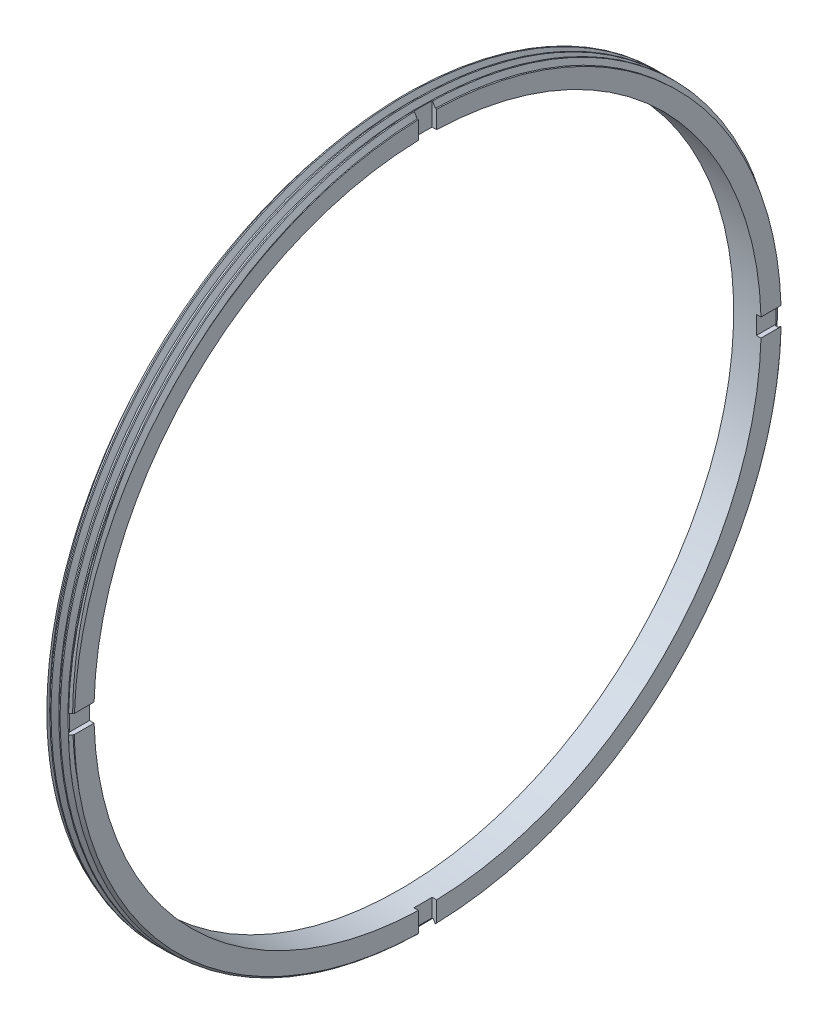
SolidWorks part; units mm, degrees
ref_plane "Přední rovina" through (0, 0, 0) normal (0, 0, 1) x (1, 0, 0)
ref_plane "Horní rovina" through (0, 0, 0) normal (0, 1, 0) x (1, 0, 0)
ref_plane "Pravá rovina" through (0, 0, 0) normal (1, 0, 0) x (0, 0, -1)
sketch "Skica1" plane through (0, 0, 0) normal (0, 0, 1) x (1, 0, 0)
  line L0 (0, 0) -> (50000, 0) construction
  line L1 (0, 36.5) -> (3, 36.5)
  line L2 (0, 36.5) -> (0, 39)
  line L3 (0, 39) -> (3, 39)
  line L4 (3, 36.5) -> (3, 39)
  dimension "D1" = 36.5
  dimension "D2" = 39
  dimension "D3" = 3
revolve "Rotovat1" add sketch "Skica1" angle 360 about L0
chamfer "Zkosení1" distance 0.3 2 edges at (3, 0, 39) (0, 0, 39)
thread "Závit1" pitch 1 start angle 0, offset 1, length 0, pitch 1, diameter 78
ref_plane "Rovina1" through (-0.7, 0, -39) normal (0, -1, 0) x (0, 0, -1)
sketch "Profil závitu1" plane through (-0.7, 0, -39) normal (0, -1, 0) x (0, 0, -1)
  line L0 (0, 0) -> (0, 1) construction
  line L11 (0, 0) -> (0, 0.875)
  line L12 (0, 0.875) -> (-0.5413, 0.5625)
  line L13 (-0.5413, 0.5625) -> (-0.5413, 0.3125)
  line L15 (-0.5413, 0.3125) -> (0, 0)
  line L17 (-0.5413, 0.4375) -> (0, 0.4375) construction
  point P2 (0, 0)
  dimension "Pitch" = 1
  dimension "Profile_Angle" = 60
  dimension "Profile_Land" = 0.25
  dimension "Profile_Height" = 0.5413
sketch "Skica5" plane through (0, 0, 0) normal (0, 1, 0) x (1, 0, 0)
  line L0 (0, 0) -> (3, 0) construction
  line L1 (3, 24.8886) -> (3, 38.6978) construction
  line L2 (2.5, 1) -> (3.5, 1)
  line L3 (2.5, 1) -> (2.5, -1)
  line L4 (2.5, -1) -> (3.5, -1)
  line L5 (3.5, 1) -> (3.5, -1)
  line L6 (2.5, 1) -> (3.5, -1) construction
  line L7 (2.5, -1) -> (3.5, 1) construction
  dimension "D1" = 2
  dimension "D2" = 1
extrude "Odebrat vysunutím1" cut sketch "Skica5" against normal through all both and the other way through all
pattern_circular "Kruhové pole1" count 2 every 90 about axis through (0, 0, 0) along (1, 0, 0) of "Odebrat vysunutím1"
